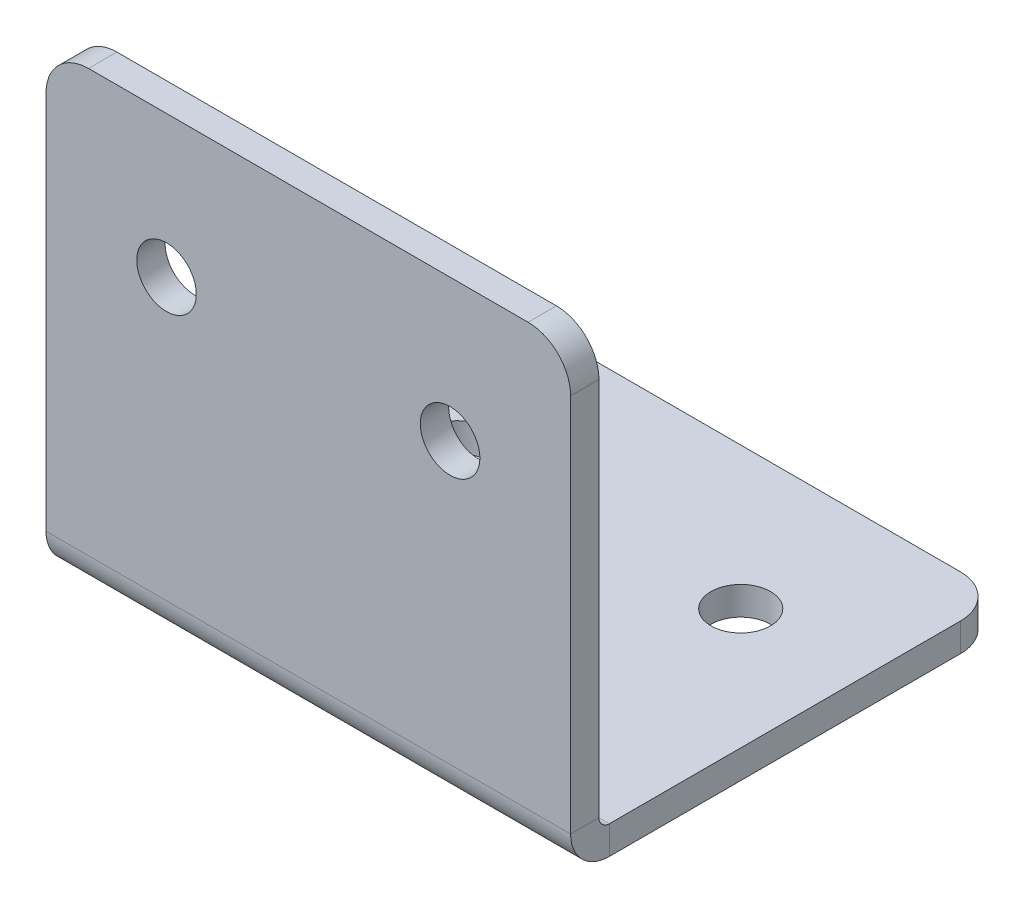
SolidWorks part; units mm, degrees
note: The reader was unsure of these and kept them because the rebuilt part matched: flange length of "边线-法兰1".
ref_plane "前视基准面" through (0, 0, 0) normal (0, 0, 1) x (1, 0, 0)
ref_plane "上视基准面" through (0, 0, 0) normal (0, 1, 0) x (1, 0, 0)
ref_plane "右视基准面" through (0, 0, 0) normal (1, 0, 0) x (0, 0, -1)
sketch "草图1" plane through (0, 0, 0) normal (0, 1, 0) x (1, 0, 0)
  line L0 (-18.5, 6.75) -> (18.5, 6.75) construction
  line L1 (-15.5, 16.75) -> (15.5, 16.75)
  line L2 (-18.5, 13.75) -> (-18.5, -13.75)
  line L3 (-18.5, -13.75) -> (18.5, -13.75)
  line L4 (18.5, 13.75) -> (18.5, -13.75)
  line L5 (0, -13.75) -> (0, 16.75) construction
  line L6 (-18.5, 0) -> (18.5, 0) construction
  circle A0 centre (-10, 6.75) radius 2.1
  circle A1 centre (10, 6.75) radius 2.1
  arc A2 (15.5, 16.75) -> (18.5, 13.75) centre (15.5, 13.75) cw
  arc A3 (-15.5, 16.75) -> (-18.5, 13.75) centre (-15.5, 13.75) ccw
  point P0 (0, 0)
  point P15 (18.5, 16.75)
  point P18 (-18.5, 16.75)
  dimension "D4" = 4.2
  dimension "D6" = 3
  dimension "D1" = 37
  dimension "D2" = 30.5
  dimension "D3" = 10
  dimension "D5" = 20
base flange "基体-法兰1" sketch "草图1" thickness 2 reverse thickness direction no parameters "D1"=0.7366
edge flange "边线-法兰1" sketch "草图8" flange angle 90 flange length 32.5 bend radius 0.7366 thickness 2 relief rectangular parameters "D6"=10
sketch "草图8" plane through (0, 0, 13.75) normal (0, 0, 1) x (1, 0, 0)
  line L0 (-18.5, 0) -> (18.5, 0) construction
  line L1 (-18.5, 0) -> (18.5, 0)
  line L2 (-18.5, 0) -> (-18.5, 27.5)
  line L3 (-15.5, 30.5) -> (15.5, 30.5)
  line L4 (18.5, 27.5) -> (18.5, 0)
  line L5 (0, 30.5) -> (0, 20.5) construction
  line L6 (0, 20.5) -> (-18.5, 20.5) construction
  circle A0 centre (-10, 20.5) radius 2.1
  circle A1 centre (10, 20.5) radius 2.1
  arc A2 (15.5, 30.5) -> (18.5, 27.5) centre (15.5, 27.5) cw
  arc A3 (-18.5, 27.5) -> (-15.5, 30.5) centre (-15.5, 27.5) cw
  point P16 (-18.5, 30.5)
  dimension "D2" = 4.2
  dimension "D5" = 3
  dimension "D1" = 30.5
  dimension "D3" = 20
  dimension "D4" = 10
bend "边线折弯1" bend radius 0.7366 bend angle 90 parameters "D5"=1
sketch "折弯-线1" plane through (0, 0, 0) normal (0, 1, 0) x (1, 0, 0)
sketch "边界框1" plane through (0, 0, 0) normal (0, 1, 0) x (1, 0, 0)
sheet metal parameters "钣金6" thickness 2 parameters "D1"=0.7366
flat pattern "平板型式6" [suppressed]
sketch "折弯-线2" plane through (0, 0, 0) normal (0, 1, 0) x (1, 0, 0)
sketch "边界框2" [suppressed] plane through (0, 0, 0) normal (0, 1, 0) x (1, 0, 0)
sheet metal parameters "钣金7" thickness 2 parameters "D1"=0.7366
flat pattern "平板型式6" [suppressed]
sketch "折弯-线2" plane through (0, 0, 0) normal (0, 1, 0) x (1, 0, 0)
sketch "边界框2" [suppressed] plane through (0, 0, 0) normal (0, 1, 0) x (1, 0, 0)
bend of the flat pattern "展平-<边线折弯1>1"
